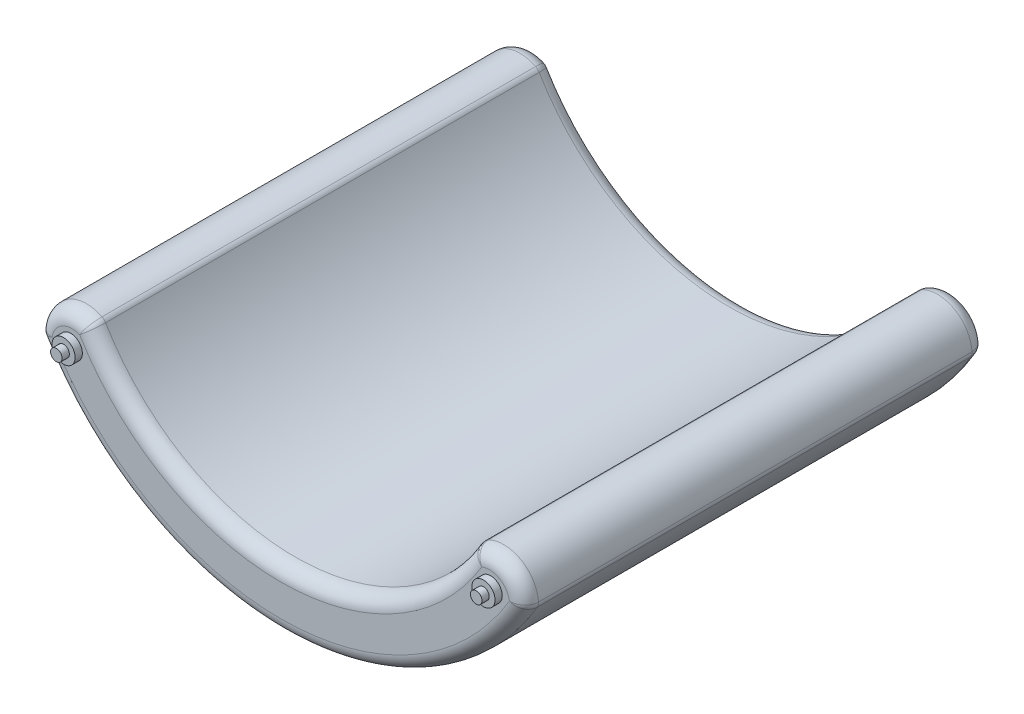
SolidWorks part; units mm, degrees
ref_plane "Front Plane" through (0, 0, 0) normal (0, 0, 1) x (1, 0, 0)
ref_plane "Top Plane" through (0, 0, 0) normal (0, 1, 0) x (1, 0, 0)
ref_plane "Right Plane" through (0, 0, 0) normal (1, 0, 0) x (0, 0, -1)
sketch "Sketch1" plane through (0, 0, 0) normal (0, 0, 1) x (1, 0, 0)
  line L0 (-65.9911, -38.1) -> (-68.5892, -39.6) construction
  line L1 (0, 0) -> (65.9911, -38.1) construction
  line L2 (-81.5796, -47.1) -> (-84.1777, -48.6) construction
  line L3 (-68.5892, -39.6) -> (-81.5796, -47.1) construction
  line L4 (0, 0) -> (-65.9911, -38.1) construction
  line L5 (81.5796, -47.1) -> (84.1777, -48.6) construction
  line L6 (68.5892, -39.6) -> (81.5796, -47.1) construction
  line L7 (-65.9911, -38.1) -> (65.9911, -38.1) construction
  line L8 (65.9911, -38.1) -> (68.5892, -39.6) construction
  arc A0 (-65.9911, -38.1) -> (65.9911, -38.1) centre (0, 0) ccw
  arc A1 (-68.5892, -39.6) -> (68.5892, -39.6) centre (0, 0) ccw
  arc A2 (-81.5796, -47.1) -> (81.5796, -47.1) centre (0, 0) ccw
  arc A3 (-84.1777, -48.6) -> (84.1777, -48.6) centre (0, 0) ccw
  arc A4 (-84.1777, -48.6) -> (-65.9911, -38.1) centre (-72.1797, -48.3812) cw
  arc A5 (-81.5796, -47.1) -> (-68.5892, -39.6) centre (-72.5969, -47.6584) cw
  arc A6 (65.9911, -38.1) -> (84.1777, -48.6) centre (72.1797, -48.3812) cw
  arc A7 (68.5892, -39.6) -> (81.5796, -47.1) centre (72.5969, -47.6584) cw
  arc A8 (81.5796, -47.1) -> (83.3261, -43.9363) centre (0, 0) ccw construction
  arc A9 (68.5892, -39.6) -> (70.2702, -36.534) centre (0, 0) ccw construction
  arc A10 (65.9911, -38.1) -> (-65.9911, -38.1) centre (0, 0) ccw construction
  arc A11 (70.2702, -36.534) -> (-70.2702, -36.534) centre (0, 0) ccw construction
  arc A12 (83.3261, -43.9363) -> (-83.3261, -43.9363) centre (0, 0) ccw construction
  arc A13 (84.1777, -48.6) -> (-84.1777, -48.6) centre (0, 0) ccw construction
  arc A14 (-83.3261, -43.9363) -> (-81.5796, -47.1) centre (0, 0) ccw construction
  arc A15 (-70.2702, -36.534) -> (-68.5892, -39.6) centre (0, 0) ccw construction
  point P6 (63.9209, -37.5791)
  point P19 (0, 0)
  dimension "D1" = 152.4
  dimension "D2" = 3
  dimension "D3" = 15
  dimension "D4" = 3
  dimension "D6" = 12
  dimension "D7" = 9
  dimension "D8" = 12
  dimension "D9" = 9
  dimension "D5" = 120
extrude "Boss-Extrude1" add sketch "Sketch1" along normal mid plane 150
fillet "Fillet1" radius 3 8 edges at (68.5892, -39.6, 0) (65.9911, -38.1, 0) (81.5796, -47.1, 0) (84.1777, -48.6, 0) (-65.9911, -38.1, 0) (-84.1777, -48.6, 0) (-68.5892, -39.6, 0) (-81.5796, -47.1, 0)
sketch "Sketch2" plane through (0, 0, 75) normal (0, 0, 1) x (1, 0, 0)
  arc A8 (84.156, -47.6278) -> (66.8264, -37.6414) centre (72.1797, -48.3812) ccw
  arc A9 (66.8264, -37.6414) -> (65.5827, -38.7988) centre (68.1647, -40.3263) ccw
  arc A10 (-65.5827, -38.7988) -> (65.5827, -38.7988) centre (0, 0) ccw
  arc A11 (-65.5827, -38.7988) -> (-66.8264, -37.6414) centre (-68.1647, -40.3263) ccw
  arc A12 (-66.8264, -37.6414) -> (-84.156, -47.6278) centre (-72.1797, -48.3812) ccw
  arc A13 (-84.156, -47.6278) -> (-83.7467, -49.339) centre (-81.1619, -47.8161) ccw
  arc A14 (-83.7467, -49.339) -> (83.7467, -49.339) centre (0, 0) ccw
  arc A15 (83.7467, -49.339) -> (84.156, -47.6278) centre (81.1619, -47.8161) ccw
  arc A16 (84.156, -47.6278) -> (66.8264, -37.6414) centre (72.1797, -48.3812) ccw
  arc A17 (66.8264, -37.6414) -> (65.5827, -38.7988) centre (68.1647, -40.3263) ccw
  arc A18 (-65.5827, -38.7988) -> (65.5827, -38.7988) centre (0, 0) ccw
  arc A19 (-65.5827, -38.7988) -> (-66.8264, -37.6414) centre (-68.1647, -40.3263) ccw
  arc A20 (-66.8264, -37.6414) -> (-84.156, -47.6278) centre (-72.1797, -48.3812) ccw
  arc A21 (-84.156, -47.6278) -> (-83.7467, -49.339) centre (-81.1619, -47.8161) ccw
  arc A22 (-83.7467, -49.339) -> (83.7467, -49.339) centre (0, 0) ccw
  arc A23 (83.7467, -49.339) -> (84.156, -47.6278) centre (81.1619, -47.8161) ccw
  dimension "D1" = 0
extrude "Boss-Extrude2" add sketch "Sketch2" along normal blind 5
fillet "Fillet2" radius 5 8 edges at (66.1209, -38.1302, 80) (78.1712, -37.984, 80) (84.0796, -48.5141, 80) (0, -97.2, 80) (-84.0796, -48.5141, 80) (-78.1712, -37.984, 80) (-66.1209, -38.1302, 80) (0, -76.2, 80)
mirror "Mirror1" about plane through (0, 0, 0) normal (0, 0, 1) of "Fillet2", "Boss-Extrude2"
ref_plane "Plane1" through (0, -47, 0) normal (0, 1, 0) x (1, 0, 0)
sketch "Sketch3" plane through (0, -47, 0) normal (0, 1, 0) x (1, 0, 0)
  line L0 (-79.0421, -80) -> (-66.2151, -80)
  line L1 (66.2151, -80) -> (79.0421, -80)
  line L2 (66.2151, -80) -> (79.0421, -80) construction
  line L3 (-79.0421, -80) -> (-66.2151, -80) construction
  line L4 (-72.6286, -80) -> (-72.6286, -85)
  line L5 (-72.6286, -85) -> (-74.6286, -85)
  line L6 (-74.6286, -85) -> (-74.6286, -82.5)
  line L7 (-74.6286, -82.5) -> (-76.6286, -82.5)
  line L8 (-76.6286, -82.5) -> (-76.6286, -80)
  line L9 (-76.6286, -80) -> (-72.6286, -80)
  dimension "D1" = 2.5
  dimension "D2" = 4
  dimension "D3" = 2
  dimension "D4" = 5
revolve "Revolve1" add sketch "Sketch3" angle 360 about L4
mirror "Mirror2" about plane through (0, 0, 0) normal (1, 0, 0) of "Revolve1"
